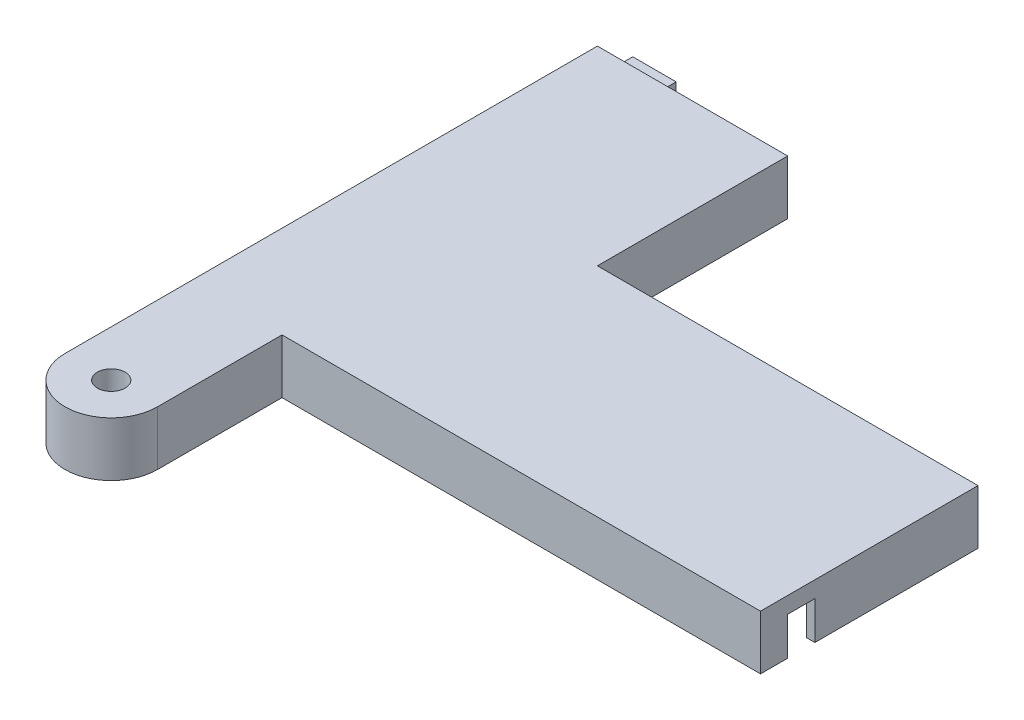
SolidWorks part; units mm, degrees
ref_plane "Front Plane" through (0, 0, 0) normal (0, 0, 1) x (1, 0, 0)
ref_plane "Top Plane" through (0, 0, 0) normal (0, 1, 0) x (1, 0, 0)
ref_plane "Right Plane" through (0, 0, 0) normal (1, 0, 0) x (0, 0, -1)
sketch "CornerrSketch1" plane through (0, 0, 0) normal (0, 1, 0) x (1, 0, 0)
  line L0 (0, 195.825) -> (70, 195.825)
  line L5 (70, 195.825) -> (70, 125.825)
  line L6 (70, 125.825) -> (210, 125.825)
  line L7 (210, 45.825) -> (210, 125.825)
  line L11 (34, 0) -> (34, 45.825)
  line L12 (34, 45.825) -> (210, 45.825)
  line L13 (0, 195.825) -> (0, 0)
  arc A0 (0, 0) -> (34, 0) centre (17, 0) ccw
  point P2 (35, 195.825)
  dimension "D3" = 34
  dimension "D4" = 70
  dimension "D2" = 80
  dimension "D1" = 45.825
  dimension "D6" = 210
  dimension "D5" = 150
extrude "CornerBoss-Extrude1" add sketch "CornerrSketch1" along normal blind 20
shell "Shell4" thickness 3 removed face at (78.5, 0, -89.7438)
sketch "PadSketch2" plane through (0, 17, 0) normal (0, -1, 0) x (1, 0, 0)
  circle A0 centre (17, 0) radius 12
  dimension "D1" = 24
extrude "PadBoss-Extrude2" add sketch "PadSketch2" along normal blind 10
sketch "StepperShaftHoleCutSketch3" plane through (0, 7, 0) normal (0, -1, 0) x (1, 0, 0)
  circle A0 centre (17, 0) radius 5.1
  dimension "D1" = 10.2
extrude "StepperShaftHoleCut-Extrude1" cut sketch "StepperShaftHoleCutSketch3" against normal through all
sketch "ThreadedNutMountHolesSketch4" plane through (0, 7, 0) normal (0, -1, 0) x (-1, 0, 0)
  circle A8 centre (-17, 8) radius 1
  circle A9 centre (-17, -8) radius 1
  circle A10 centre (-25, 0) radius 1
  circle A11 centre (-9, 0) radius 1
  dimension "D1" = 2
  dimension "D3" = 16
  dimension "D4" = 8
  dimension "D5" = 16
extrude "ThreadedNutMountHolesCut-Extrude2" cut sketch "ThreadedNutMountHolesSketch4" against normal blind 10
sketch "BRPegHoleSketch1" plane through (210, 0, 0) normal (1, 0, 0) x (0, 0, -1)
  line L1 (55.825, 14) -> (65.825, 14)
  line L2 (55.825, 14) -> (55.825, 0)
  line L3 (55.825, 0) -> (65.825, 0)
  line L4 (65.825, 14) -> (65.825, 0)
  line L6 (45.825, 0) -> (125.825, 0) construction
  line L7 (45.825, 20) -> (45.825, 0) construction
  dimension "D2" = 10
  dimension "D3" = 14
  dimension "D1" = 10
extrude "BRPegHoleCut-Extrude1" cut sketch "BRPegHoleSketch1" against normal blind 3
sketch "TopPegSketch2" plane through (0, 0, -195.825) normal (0, 0, -1) x (-1, 0, 0)
  line L0 (0, 20) -> (0, 0) construction
  line L1 (-19.9, 13.9) -> (-10.1, 13.9)
  line L2 (-19.9, 13.9) -> (-19.9, 0)
  line L3 (-19.9, 0) -> (-10.1, 0)
  line L4 (-10.1, 13.9) -> (-10.1, 0)
  line L6 (-70, 0) -> (0, 0) construction
  dimension "D2" = 13.9
  dimension "D3" = 9.8
  dimension "D1" = 10.1
extrude "TopPegBoss-Extrude1" add sketch "TopPegSketch2" along normal blind 3
sketch "TopPegCapSketch3" plane through (0, 0, -198.825) normal (0, 0, -1) x (-1, 0, 0)
  line L1 (-22.9, 17) -> (-6.9, 17)
  line L2 (-22.9, 17) -> (-22.9, 0)
  line L3 (-22.9, 0) -> (-6.9, 0)
  line L4 (-6.9, 17) -> (-6.9, 0)
  line L5 (-19.9, 0) -> (-10.1, 0) construction
  line L7 (-19.9, 13.9) -> (-19.9, 0) construction
  dimension "D1" = 16
  dimension "D3" = 17
  dimension "D2" = 3
extrude "TopPegCapBoss-Extrude2" add sketch "TopPegCapSketch3" along normal blind 3.1
sketch "CenterPegHoleCutSketch1" plane through (0, 0, -125.825) normal (0, 0, -1) x (-1, 0, 0)
  line L0 (-210, 0) -> (-70, 0) construction
  line L1 (-180, 14) -> (-170, 14)
  line L2 (-180, 14) -> (-180, 0)
  line L3 (-180, 0) -> (-170, 0)
  line L4 (-170, 14) -> (-170, 0)
  line L6 (-70, 20) -> (-70, 0) construction
  dimension "D2" = 10
  dimension "D1" = 14
  dimension "D3" = 100
extrude "CenterPegHoleCut-Extrude1" cut sketch "CenterPegHoleCutSketch1" against normal blind 3
equation "\"RailThickness\"= .125in'Spec"
equation "\"StepperMountingHoleDistance\"= 31mm'Spec"
equation "\"StepperMountingHoleOffsetFromLeftOrRightSide\"= \"StepperMountingHoleOffsetFromItsSide\" + \"RailThickness\""
equation "\"StepperMountingHoleOffsetFromItsSide\"= 5.5mm'Spec"
equation "\"FrontBackRailLength\"= 510mm"
equation "\"DistanceBetweenLeftToRightStepperHoles\"= \"FrontBackRailLength\" - \"StepperMountingHoleOffsetFromLeftOrRightSide\" * 2 - \"StepperMountingHoleDistance\"'Equals 461.65"
equation "\"BedThickness\"= 20mm"
equation "\"BedLLongSide\"= \"BedThirdSize\" * 3'Equals 210"
equation "\"BedLShortSide\"= \"BedThirdSize\" * 2'Equals 140"
equation "\"BedLWidth\"= \"BedThirdSize\"'Equals 70"
equation "\"D4@CornerrSketch1\"=\"BedLWidth\" + \"BedIncreasedByLength\"/2"
equation "\"BedIncreasedByWidth\"= 20mm"
equation "\"BedIncreasedByLength\"= 0mm"
equation "\"BedThirdSize\"= 70mm"
equation "\"BedWidth\"= \"BedInnerSquareWidth\" + \"BedLWidth\" * 2 + \"BedIncreasedByWidth\"'Equals 370"
equation "\"BedInnerSquareWidth\"= \"BedThirdSize\" * 3'Equals 210"
equation "\"StandardWallThickness\"= 3mm"
equation "\"D2@BRPegHoleSketch1\"=\"BedPegHoleWidth\""
equation "\"D1@BRPegHoleSketch1\"=\"BedTopPegOffsetFromSide\" "
equation "\"D3@BRPegHoleSketch1\"=\"BedPegHoleHeight\""
equation "\"D1@BRPegHoleCut-Extrude1\" = \"StandardWallThickness\""
equation "\"D2@TopPegSketch2\"=\"BedPegHeight\""
equation "\"D1@TopPegBoss-Extrude1\" = \"StandardWallThickness\""
equation "\"D3@TopPegCapSketch3\"=\"BedPegCapHeight\""
equation "\"D1@TopPegCapSketch3\"=\"BedPegCapWidth\""
equation "\"D1@TopPegCapBoss-Extrude2\"=\"BedPegBoss\""
equation "\"D2@TopPegCapSketch3\"=\"StandardWallThickness\""
equation "\"DistanceFromBedSideToStepperHole\"= ( \"DistanceBetweenLeftToRightStepperHoles\" - \"BedWidth\" ) / 2'Equals 45.825"
equation "\"DistanceFromBedFrontToFirstLeftStepperHole\"= \"LeadScrewNutPadSize\" + 10mm'Equals 34"
equation "\"D3@CornerrSketch1\"=\"DistanceFromBedFrontToFirstLeftStepperHole\""
equation "\"LeadScrewNutPadSize\"= \"LeadScrewNutMountingHoleFlangeDiameter\" + 2mm'Equals 24"
equation "\"D1@PadSketch2\" = \"LeadScrewNutPadSize\""
equation "\"D1@StepperShaftHoleCutSketch3\"=\"LeadScrewNutInnerShaftFlangeDiameter\""
equation "\"D2@CornerrSketch1\"=\"BedLWidth\" + \"BedIncreasedByWidth\"/2"
equation "\"D6@CornerrSketch1\"=\"BedLLongSide\""
equation "\"D1@TopPegSketch2\"=\"BedTopPegOffsetFromSide\" + .1mm"
equation "\"D1@CornerrSketch1\"=\"DistanceFromBedSideToStepperHole\""
equation "\"D5@CornerrSketch1\"=\"BedLShortSide\" + \"BedIncreasedByWidth\"/2"
equation "\"LeadScrewNutInnerShaftFlangeDiameter\"= 10.2mm'Spec"
equation "\"LeadScrewNutMountHoleDiameter\"= 2mm'Spec is 4.1 but smaller for tapping"
equation "\"LeadScrewNutMountingHoleFlangeDiameter\"= 22mm'Spec"
equation "\"LeadScrewNutMountingHoleDistance\"= 16mm'Spec"
equation "\"D1@ThreadedNutMountHolesSketch4\"=\"LeadScrewNutMountHoleDiameter\""
equation "\"D2@ThreadedNutMountHolesSketch4\"=\"LeadScrewNutMountingHoleDistance\"/2"
equation "\"D3@ThreadedNutMountHolesSketch4\"=\"LeadScrewNutMountingHoleDistance\""
equation "\"D4@ThreadedNutMountHolesSketch4\"=\"LeadScrewNutMountingHoleDistance\"/2"
equation "\"D5@ThreadedNutMountHolesSketch4\"=\"LeadScrewNutMountingHoleDistance\""
equation "\"LeadScrewNutPadDepth\"= \"BedThickness\" / 2'Equals 10"
equation "\"D1@PadBoss-Extrude2\"=\"LeadScrewNutPadDepth\""
equation "\"D1@ThreadedNutMountHolesCut-Extrude2\"= \"LeadScrewNutPadDepth\""
equation "\"BedPegHoleWidth\"= 10mm"
equation "\"BedPegHoleHeight\"= \"BedThickness\" - \"StandardWallThickness\" * 2'Equals 14"
equation "\"BedPegWidth\"= \"BedPegHoleWidth\" - .1mm * 2'For easier assembly"
equation "\"BedPegHeight\"= \"BedPegHoleHeight\" - .1mm'For easier assembly"
equation "\"BedTopPegOffsetFromSide\"= 10mm"
equation "\"BedPegBoss\"= \"StandardWallThickness\" + .1mm'For easier assembly"
equation "\"BedPegCapHeight\"= \"BedThickness\" - \"StandardWallThickness\"'Equals 17"
equation "\"BedPegCapWidth\"= \"BedThickness\" / 2 + \"StandardWallThickness\" * 2'Equals 16"
equation "\"D3@TopPegSketch2\"=\"BedPegWidth\""
equation "\"D1@CenterPegHoleCutSketch1\" = \"BedPegHoleHeight\""
equation "\"D2@CenterPegHoleCutSketch1\" = \"BedPegHoleWidth\""
equation "\"D3@CenterPegHoleCutSketch1\"= \"BedInnerSquareWidth\"/2 - \"BedPegHoleWidth\"/2"
equation "\"D1@CenterPegHoleCut-Extrude1\"=\"StandardWallThickness\""
